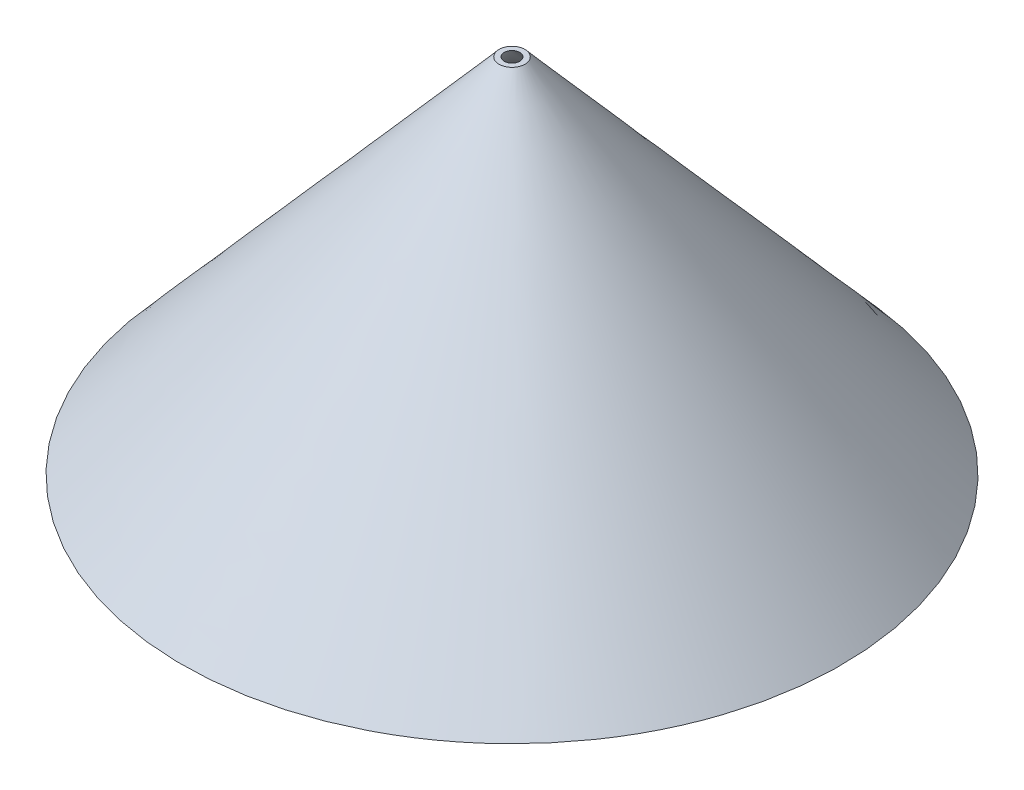
SolidWorks part; units mm, degrees
ref_plane "Front Plane" through (0, 0, 0) normal (0, 0, 1) x (1, 0, 0)
ref_plane "Top Plane" through (0, 0, 0) normal (0, 1, 0) x (1, 0, 0)
ref_plane "Right Plane" through (0, 0, 0) normal (1, 0, 0) x (0, 0, -1)
sketch "Sketch1" plane through (0, 0, 0) normal (0, 1, 0) x (1, 0, 0)
  circle A0 centre (0, 0) radius 127.5
  dimension "D1" = 255
ref_plane "Plane1" through (0, 140, 0) normal (0, 1, 0) x (1, 0, 0)
sketch "Sketch2" plane through (0, 140, 0) normal (0, 1, 0) x (1, 0, 0)
  circle A0 centre (0, 0) radius 5
  dimension "D1" = 10
loft "Loft1" add profiles "Sketch2", "Sketch1" connector at (-4.4392, 140, -2.3007) connector at (-97.1077, 0, -82.6217)
sketch "Sketch3" plane through (0, 140, 0) normal (0, 1, 0) x (1, 0, 0)
  circle A0 centre (0, 0) radius 3
  dimension "D1" = 6
sketch "Sketch4" plane through (0, 0, 0) normal (0, 1, 0) x (1, 0, 0)
  circle A0 centre (0, 0) radius 123
  dimension "D1" = 246
loft "Cut-Loft1" cut profiles "Sketch4", "Sketch3" connector at (113.2791, 0, -47.9255) connector at (1.4683, 140, -2.6161)
